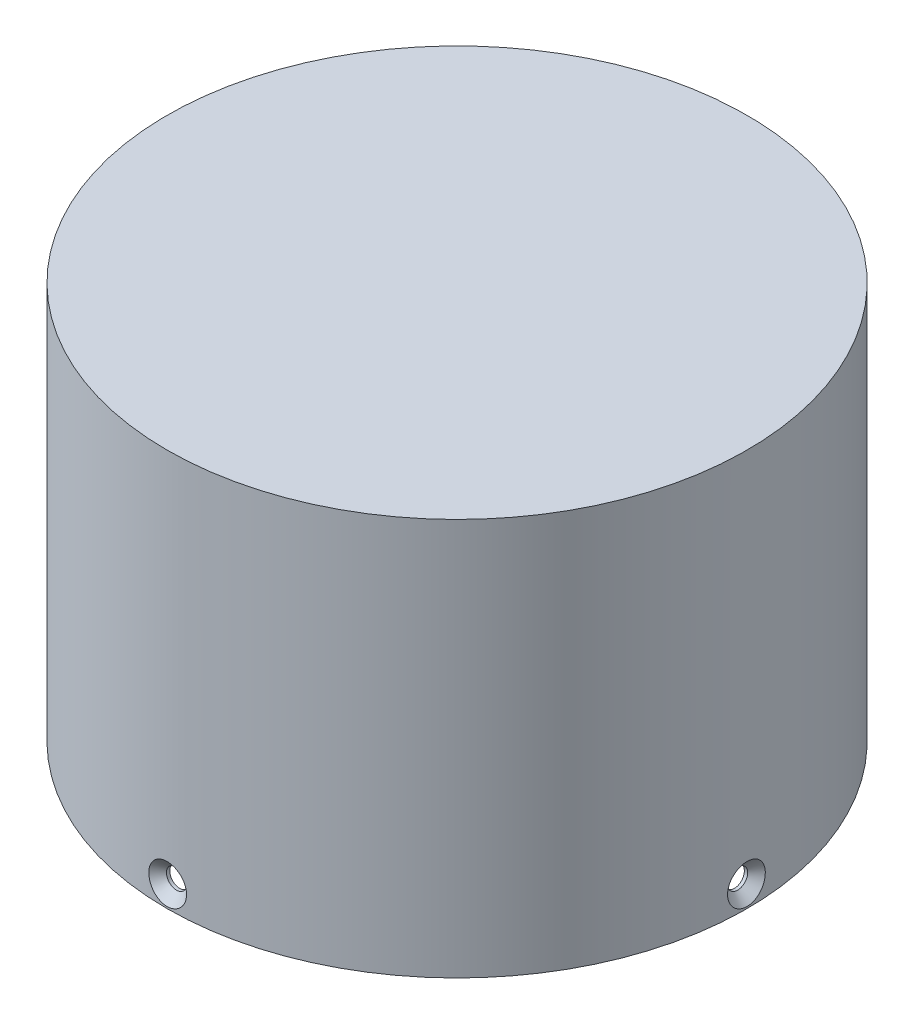
SolidWorks part; units mm, degrees
ref_plane "Front Plane" through (0, 0, 0) normal (0, 0, 1) x (1, 0, 0)
ref_plane "Top Plane" through (0, 0, 0) normal (0, 1, 0) x (1, 0, 0)
ref_plane "Right Plane" through (0, 0, 0) normal (1, 0, 0) x (0, 0, -1)
sketch "Sketch3" plane through (0, 0, 0) normal (0, 1, 0) x (1, 0, 0)
  circle A0 centre (0, 0) radius 23.075
  dimension "D1" = 46.15
extrude "Boss-Extrude3" add sketch "Sketch3" along normal blind 31.6
sketch "Sketch4" plane through (0, 0, 0) normal (0, -1, 0) x (1, 0, 0)
  circle A0 centre (0, 0) radius 22.075
  dimension "D1" = 44.15
extrude "Cut-Extrude1" cut sketch "Sketch4" against normal blind 30.6
hole_wizard "CSK for M2 Flat Head Machine Screw2" positions "3DSketch1" profile "Sketch5" countersink size "M2" standard "ANSI Metric" end condition up to next
sketch3d "3DSketch1"
  point P0 (23.075, 1.7, 0)
  point P3 (0, 0, 0)
  point P4 (0, 0, 0)
  point P5 (0, 0, 0)
  point P6 (0, 0, 0)
  point P7 (0, 0, 0)
  point P8 (0, 0, 0)
sketch "Sketch5" plane through (23.075, 1.7, 0) normal (0, 1, 0) x (0, 0, -1)
  line L0 (0, 0) -> (0, 1)
  line L1 (0, 1) -> (0.8, 1)
  line L2 (0.8, 1) -> (0.8, 0.75)
  line L3 (0.8, 0.75) -> (1.55, 0)
  line L5 (1.55, 0) -> (0, 0)
  line L6 (-0.8, 0.75) -> (-1.55, 0) construction
  line L11 (0, -6.35) -> (0, 107.95) construction
  dimension "Thru Hole Dia." = 1.6
  dimension "Thru Hole Depth" = 1
  dimension "Near C'Sink Dia." = 3.1
  dimension "Near C'Sink Angle" = 90
ref_axis "Axis1" through (0, 30.6, 0) along (0, -1, 0)
pattern_circular "CirPattern1" count 4 over 360 about axis through (0, 30.6, 0) along (0, -1, 0) of "CSK for M2 Flat Head Machine Screw2"
